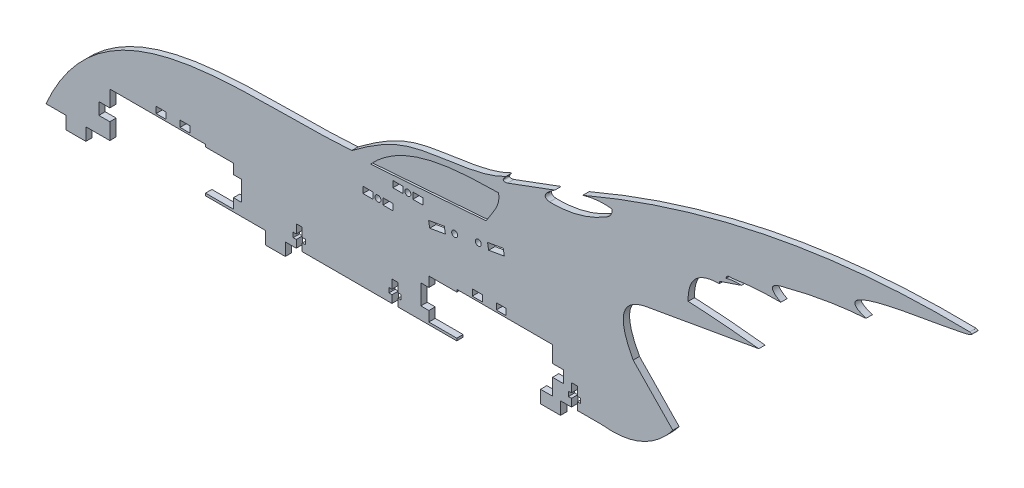
SolidWorks part; units mm, degrees
ref_plane "前视基准面" through (0, 0, 0) normal (0, 0, 1) x (1, 0, 0)
ref_plane "上视基准面" through (0, 0, 0) normal (0, 1, 0) x (1, 0, 0)
ref_plane "右视基准面" through (0, 0, 0) normal (1, 0, 0) x (0, 0, -1)
sketch "Sketch1" plane through (0, 0, 0) normal (0, 0, 1) x (1, 0, 0)
  line L0 (-360, 0) -> (360, 0) construction
  line L1 (-19.5671, 50.1455) -> (753.6757, 55.0373) construction
  line L2 (-32.114, 89.2833) -> (541.2194, 89.2833) construction
sketch "Sketch2" plane through (0, 0, 0) normal (0, 0, 1) x (1, 0, 0)
  line L0 (-171.469, -34.0766) -> (107.0727, -34.0766)
  spline S0 degree 2 poles (291.7809, 98.4714) (190.6089, 100.5394) (97.7379, 60.7759) knots 0 0 0 1 1 1
  spline S1 degree 2 poles (97.7379, 60.7759) (104.9288, 63.0011) (112.3796, 62.1565) knots 0 0 0 1 1 1
  spline S2 degree 2 poles (112.3796, 62.1565) (112.7301, 59.0518) (109.5504, 57.3117) knots 0 0 0 1 1 1
  spline S3 degree 2 poles (109.5504, 57.3117) (96.53, 49.2469) (81.0586, 49.5528) knots 0 0 0 1 1 1
  spline S4 degree 2 poles (81.0586, 49.5528) (75.6423, 50.628) (83.6966, 55.9983) knots 0 0 0 1 1 1
  spline S5 degree 1 poles (83.6966, 55.9983) (60.0234, 47.198) knots 0 0 1 1
  spline S6 degree 2 poles (60.0234, 47.198) (56.1503, 46.2452) (59.1238, 49.6133) knots 0 0 0 1 1 1
  spline S7 degree 3 poles (59.1238, 49.6133) (44.2925, 41.9215) (13.2093, 43.4053) (-7.7072, 29.9938) (-18.1066, 22.3013) knots 0 0 0 0 0.606339 1 1 1 1
  spline S8 degree 3 poles (-18.1066, 22.3013) (-73.3001, 18.1787) (-142.3815, 32.9288) (-171.469, -34.0766) knots 0 0 0 0 1 1 1 1
  spline S9 degree 2 poles (107.0727, -34.0766) (128.9682, -36.583) (142.8921, -18.7155) knots 0 0 0 1 1 1
  spline S10 degree 2 poles (166.2115, 56.6) (150.1116, 56.4482) (150.5886, 41.1327) knots 0 0 0 1 1 1
  spline S11 degree 2 poles (150.5886, 41.1327) (168.3325, 40.2418) (185.983, 38.2447) knots 0 0 0 1 1 1
  spline S12 degree 1 poles (185.983, 38.2447) (129.8121, 28.3469) knots 0 0 1 1
  spline S13 degree 2 poles (129.8121, 28.3469) (110.3675, 24.8357) (122.9996, 1.8225) knots 0 0 0 1 1 1
  spline S14 degree 1 poles (122.9996, 1.8225) (142.8921, -18.7155) knots 0 0 1 1
  spline S25 degree 1 poles (166.2115, 56.6) (166.2327, 57.6697) knots 0 0 1 1
  spline S26 degree 1 poles (166.2327, 57.6697) (177.2433, 61.4033) knots 0 0 1 1
  spline S27 degree 2 poles (177.2433, 61.4033) (173.3395, 61.7966) (169.6271, 60.6108) knots 0 0 0 1 1 1
  spline S28 degree 2 poles (169.6271, 60.6108) (169.7629, 62.5449) (172.4023, 62.1565) knots 0 0 0 1 1 1
  spline S29 degree 2 poles (172.4023, 62.1565) (184.6173, 64.0415) (197.0298, 63.9473) knots 0 0 0 1 1 1
  spline S30 degree 2 poles (197.0298, 63.9473) (187.7347, 69.0696) (198.9644, 71.4021) knots 0 0 0 1 1 1
  spline S31 degree 2 poles (198.9644, 71.4021) (219.0035, 76.7865) (239.7646, 78.3299) knots 0 0 0 1 1 1
  spline S32 degree 3 poles (291.7809, 98.4714) (303.0909, 95.7177) (210.844, 88.0264) (239.7646, 78.3299) knots 0 0 0 0 1 1 1 1
extrude "Boss-Extrude1" add sketch "Sketch2" along normal blind 3.175
sketch "Sketch3" plane through (0, 0, 3.175) normal (0, 0, 1) x (1, 0, 0)
  line L0 (-156.469, -23.0187) -> (-156.469, -49.8356) construction
  line L1 (-161.469, -34.0766) -> (-151.469, -34.0766)
  line L2 (-171.469, -34.0766) -> (107.0727, -34.0766) construction
  line L3 (-161.469, -34.0766) -> (-161.469, -40.4266)
  line L4 (-161.469, -40.4266) -> (-151.469, -40.4266)
  line L5 (-151.469, -40.4266) -> (-151.469, -34.0766)
  line L6 (-106.469, -7.8183) -> (-106.469, -55.0925) construction
  line L7 (-56.469, -23.0187) -> (-56.469, -49.8356) construction
  line L8 (-61.469, -40.4266) -> (-61.469, -34.0766)
  line L9 (-51.469, -40.4266) -> (-61.469, -40.4266)
  line L10 (-51.469, -34.0766) -> (-51.469, -40.4266)
  line L11 (-51.469, -34.0766) -> (-61.469, -34.0766)
  line L12 (-37.469, -5.6354) -> (-37.469, -55.0925) construction
  line L13 (81.531, -23.0187) -> (81.531, -49.8356) construction
  line L14 (76.531, -40.4266) -> (76.531, -34.0766)
  line L15 (86.531, -40.4266) -> (76.531, -40.4266)
  line L16 (86.531, -34.0766) -> (86.531, -40.4266)
  line L17 (86.531, -34.0766) -> (76.531, -34.0766)
  point P6 (-156.469, -34.0766)
  dimension "D1" = 10
  dimension "D2" = 15
  dimension "D3" = 6.35
  dimension "D4" = 100
  dimension "D5" = 238
extrude "Boss-Extrude2" add sketch "Sketch3" against normal blind 3.175
sketch "Sketch4" plane through (0, 0, 3.175) normal (0, 0, 1) x (1, 0, 0)
  line L0 (-8.7353, 21.0767) -> (49.2725, 25.4437)
  spline S0 degree 3 poles (55.4358, 40.7209) (33.0546, 40.3601) (7.8741, 39.273) (-8.7353, 21.0767) knots 0 0 0 0 1 1 1 1
  spline S1 degree 3 poles (55.4358, 40.7209) (56.7107, 34.9555) (51.7522, 29.9519) (49.2725, 25.4437) knots 0 0 0 0 1 1 1 1
extrude "Cut-Extrude1" cut sketch "Sketch4" against normal blind 1
sketch "Sketch5" plane through (0, 0, 3.175) normal (0, 0, 1) x (1, 0, 0)
  line L0 (-44.469, -4.9545) -> (-44.469, -56.9042) construction
  line L1 (-45.969, -34.0766) -> (-42.969, -34.0766)
  line L2 (-151.469, -34.0766) -> (-61.469, -34.0766) construction
  line L3 (-45.969, -34.0766) -> (-45.969, -30.2766)
  line L4 (-45.969, -23.4266) -> (-42.969, -23.4266)
  line L5 (-42.969, -23.4266) -> (-42.969, -27.8766)
  line L6 (-161.469, -40.4266) -> (-151.469, -40.4266) construction
  line L7 (-41.419, -27.8766) -> (-41.419, -30.2766)
  line L8 (-47.519, -27.8766) -> (-47.519, -30.2766)
  line L9 (-47.519, -27.8766) -> (-45.969, -27.8766)
  line L10 (-47.519, -30.2766) -> (-45.969, -30.2766)
  line L11 (-47.519, -29.0766) -> (-93.8427, -29.0766) construction
  line L12 (-161.469, -34.0766) -> (-161.469, -40.4266) construction
  line L13 (-42.969, -27.8766) -> (-41.419, -27.8766)
  line L14 (-42.969, -30.2766) -> (-41.419, -30.2766)
  line L15 (-45.969, -27.8766) -> (-45.969, -23.4266)
  line L16 (-42.969, -30.2766) -> (-42.969, -34.0766)
  line L17 (-20.469, -10.7451) -> (-20.469, -65.5516) construction
  line L18 (3.531, -4.9545) -> (3.531, -56.9042) construction
  line L19 (2.031, -30.2766) -> (2.031, -34.0766)
  line L20 (5.031, -27.8766) -> (5.031, -23.4266)
  line L21 (2.031, -30.2766) -> (0.481, -30.2766)
  line L22 (2.031, -27.8766) -> (0.481, -27.8766)
  line L23 (6.581, -30.2766) -> (5.031, -30.2766)
  line L24 (6.581, -27.8766) -> (5.031, -27.8766)
  line L25 (6.581, -27.8766) -> (6.581, -30.2766)
  line L26 (0.481, -27.8766) -> (0.481, -30.2766)
  line L27 (2.031, -23.4266) -> (2.031, -27.8766)
  line L28 (5.031, -23.4266) -> (2.031, -23.4266)
  line L29 (5.031, -34.0766) -> (5.031, -30.2766)
  line L30 (5.031, -34.0766) -> (2.031, -34.0766)
  line L31 (24.531, -8.6696) -> (24.531, -64.6722) construction
  line L32 (93.531, -4.9545) -> (93.531, -56.9042) construction
  line L33 (92.031, -30.2766) -> (92.031, -34.0766)
  line L34 (95.031, -27.8766) -> (95.031, -23.4266)
  line L35 (92.031, -30.2766) -> (90.481, -30.2766)
  line L36 (92.031, -27.8766) -> (90.481, -27.8766)
  line L37 (96.581, -30.2766) -> (95.031, -30.2766)
  line L38 (96.581, -27.8766) -> (95.031, -27.8766)
  line L39 (96.581, -27.8766) -> (96.581, -30.2766)
  line L40 (90.481, -27.8766) -> (90.481, -30.2766)
  line L41 (92.031, -23.4266) -> (92.031, -27.8766)
  line L42 (95.031, -23.4266) -> (92.031, -23.4266)
  line L43 (95.031, -34.0766) -> (95.031, -30.2766)
  line L44 (95.031, -34.0766) -> (92.031, -34.0766)
  point P6 (-44.469, -34.0766)
  dimension "D1" = 3
  dimension "D2" = 17
  dimension "D3" = 6.1
  dimension "D4" = 5
  dimension "D5" = 117
  dimension "D6" = 2.4
  dimension "D7" = 165
  dimension "D8" = 255
extrude "Cut-Extrude2" cut sketch "Sketch5" against normal through all
sketch "Sketch7" plane through (0, 0, 3.175) normal (0, 0, 1) x (1, 0, 0)
  line L0 (-91.469, -32.8766) -> (-77.469, -32.8766)
  line L1 (-139.469, -34.0766) -> (-139.469, -25.8766)
  line L2 (-151.469, -34.0766) -> (-61.469, -34.0766) construction
  line L3 (-139.469, -11.6766) -> (-91.469, -11.6766)
  line L4 (-91.469, -11.6766) -> (-91.469, -12.8766)
  line L5 (-139.469, -34.0766) -> (-91.469, -34.0766)
  line L6 (-155.6863, -22.8766) -> (-79.2758, -22.8766) construction
  line L7 (-91.469, -12.8766) -> (-77.469, -12.8766)
  line L8 (-77.469, -12.8766) -> (-77.469, -17.8766)
  line L9 (-91.469, -32.8766) -> (-91.469, -34.0766)
  line L10 (-139.469, -19.8766) -> (-144.969, -19.8766)
  line L11 (-139.469, -25.8766) -> (-144.969, -25.8766)
  line L12 (-144.969, -19.8766) -> (-144.969, -25.8766)
  line L13 (-139.469, -19.8766) -> (-139.469, -11.6766)
  line L14 (-77.469, -17.8766) -> (-73.469, -17.8766)
  line L15 (-77.469, -27.8766) -> (-73.469, -27.8766)
  line L16 (-73.469, -17.8766) -> (-73.469, -27.8766)
  line L17 (-77.469, -27.8766) -> (-77.469, -32.8766)
  line L18 (-28.469, 4.1122) -> (-28.469, -62.6854) construction
  line L19 (98.7482, -22.8766) -> (22.3377, -22.8766) construction
  line L20 (20.531, -27.8766) -> (20.531, -32.8766)
  line L21 (16.531, -17.8766) -> (16.531, -27.8766)
  line L22 (20.531, -27.8766) -> (16.531, -27.8766)
  line L23 (20.531, -17.8766) -> (16.531, -17.8766)
  line L24 (82.531, -19.8766) -> (82.531, -11.6766)
  line L25 (88.031, -19.8766) -> (88.031, -25.8766)
  line L26 (82.531, -25.8766) -> (88.031, -25.8766)
  line L27 (82.531, -19.8766) -> (88.031, -19.8766)
  line L28 (34.531, -32.8766) -> (34.531, -34.0766)
  line L29 (20.531, -12.8766) -> (20.531, -17.8766)
  line L30 (34.531, -12.8766) -> (20.531, -12.8766)
  line L31 (82.531, -34.0766) -> (34.531, -34.0766)
  line L32 (34.531, -11.6766) -> (34.531, -12.8766)
  line L33 (82.531, -11.6766) -> (34.531, -11.6766)
  line L34 (82.531, -34.0766) -> (82.531, -25.8766)
  line L35 (34.531, -32.8766) -> (20.531, -32.8766)
  line L36 (-120.2067, -9.1491) -> (-44.1643, -9.1491) construction
  line L37 (-107.769, -0.3828) -> (-107.769, -8.179) construction
  line L38 (-111.269, -10.7366) -> (-116.269, -10.7366)
  line L39 (-111.269, -10.7366) -> (-111.269, -7.5616)
  line L40 (-111.269, -7.5616) -> (-116.269, -7.5616)
  line L41 (-116.269, -10.7366) -> (-116.269, -7.5616)
  line L42 (-111.269, -10.7366) -> (-116.269, -7.5616) construction
  line L43 (-111.269, -7.5616) -> (-116.269, -10.7366) construction
  line L44 (-104.269, -7.5616) -> (-99.269, -10.7366) construction
  line L45 (-104.269, -10.7366) -> (-99.269, -7.5616) construction
  line L46 (-99.269, -10.7366) -> (-99.269, -7.5616)
  line L47 (-104.269, -7.5616) -> (-99.269, -7.5616)
  line L48 (-104.269, -10.7366) -> (-104.269, -7.5616)
  line L49 (-104.269, -10.7366) -> (-99.269, -10.7366)
  line L50 (47.331, -10.7366) -> (42.331, -7.5616) construction
  line L51 (47.331, -7.5616) -> (42.331, -10.7366) construction
  line L52 (54.331, -7.5616) -> (59.331, -10.7366) construction
  line L53 (54.331, -10.7366) -> (59.331, -7.5616) construction
  line L54 (47.331, -10.7366) -> (42.331, -10.7366)
  line L55 (47.331, -10.7366) -> (47.331, -7.5616)
  line L56 (47.331, -7.5616) -> (42.331, -7.5616)
  line L57 (42.331, -10.7366) -> (42.331, -7.5616)
  line L58 (59.331, -10.7366) -> (59.331, -7.5616)
  line L59 (54.331, -7.5616) -> (59.331, -7.5616)
  line L60 (54.331, -10.7366) -> (54.331, -7.5616)
  line L61 (54.331, -10.7366) -> (59.331, -10.7366)
  point P43 (-113.769, -9.1491)
  point P54 (-101.769, -9.1491)
  point P63 (44.831, -9.1491)
  point P64 (56.831, -9.1491)
  dimension "D3" = 48
  dimension "D1" = 32
  dimension "D2" = 22.4
  dimension "D4" = 20
  dimension "D5" = 14
  dimension "D6" = 6
  dimension "D7" = 5.5
  dimension "D8" = 4
  dimension "D9" = 10
  dimension "D10" = 90
  dimension "D11" = 12
  dimension "D12" = 23.2
  dimension "D13" = 0.94
  dimension "D14" = 3.175
  dimension "D15" = 5
extrude "Cut-Extrude3" cut sketch "Sketch7" against normal through all
sketch "Sketch8" plane through (0, 0, 3.175) normal (0, 0, 1) x (1, 0, 0)
  line L0 (0, 0) -> (0, 6) construction
  line L1 (0, 6) -> (50.4572, 14.897) construction
  line L2 (32.7597, 50.5612) -> (39.3923, 12.9459) construction
  line L3 (20.9566, 8.0832) -> (28.8351, 9.4724)
  line L4 (28.8351, 9.4724) -> (28.2838, 12.5992)
  line L5 (20.9566, 8.0832) -> (20.4053, 11.21)
  line L6 (20.4053, 11.21) -> (28.2838, 12.5992)
  line L7 (24.8959, 8.7778) -> (23.4697, 16.8657) construction
  line L8 (54.4401, 13.9873) -> (53.014, 22.0752) construction
  line L9 (57.828, 17.8086) -> (49.9495, 16.4194)
  line L10 (58.3793, 14.6819) -> (57.828, 17.8086)
  line L11 (50.5009, 13.2927) -> (49.9495, 16.4194)
  line L12 (58.3793, 14.6819) -> (50.5009, 13.2927)
  circle A0 centre (33.4835, 11.904) radius 1.5
  circle A1 centre (45.3012, 13.9878) radius 1.5
  point P8 (28.5594, 11.0358)
  dimension "D7" = 3
  dimension "D1" = 6
  dimension "D2" = 100
  dimension "D3" = 40
  dimension "D4" = 3.175
  dimension "D5" = 8
  dimension "D6" = 30
  dimension "D8" = 12
extrude "Cut-Extrude4" cut sketch "Sketch8" against normal through all
sketch "Sketch9" plane through (0, 0, 3.175) normal (0, 0, 1) x (1, 0, 0)
  line L0 (10, 32.0127) -> (10, 0) construction
  line L1 (-14.9157, 18) -> (23.6696, 18) construction
  line L2 (2.5, 19.5875) -> (7.5, 16.4125) construction
  line L3 (17.5, 16.4125) -> (12.5, 16.4125)
  line L4 (17.5, 16.4125) -> (17.5, 19.5875)
  line L5 (17.5, 19.5875) -> (12.5, 19.5875)
  line L6 (12.5, 16.4125) -> (12.5, 19.5875)
  line L7 (17.5, 16.4125) -> (12.5, 19.5875) construction
  line L8 (17.5, 19.5875) -> (12.5, 16.4125) construction
  line L9 (2.5, 16.4125) -> (7.5, 19.5875) construction
  line L10 (7.5, 16.4125) -> (7.5, 19.5875)
  line L11 (2.5, 19.5875) -> (7.5, 19.5875)
  line L12 (2.5, 16.4125) -> (2.5, 19.5875)
  line L13 (2.5, 16.4125) -> (7.5, 16.4125)
  line L14 (-5, 12.4125) -> (-5, -3.1137) construction
  line L15 (-20.9752, 8) -> (1.55, 8) construction
  line L17 (-12.5, 6.4125) -> (-7.5, 6.4125)
  line L18 (-12.5, 6.4125) -> (-12.5, 9.5875)
  line L19 (2.5, 6.4125) -> (-2.5, 9.5875) construction
  line L20 (-7.5, 6.4125) -> (-7.5, 9.5875)
  line L21 (-12.5, 9.5875) -> (-7.5, 6.4125) construction
  line L23 (-12.5, 9.5875) -> (-7.5, 9.5875)
  line L25 (2.5, 9.5875) -> (-2.5, 6.4125) construction
  line L26 (-12.5, 6.4125) -> (-7.5, 9.5875) construction
  line L28 (2.5, 9.5875) -> (-2.5, 9.5875)
  line L29 (-2.5, 6.4125) -> (-2.5, 9.5875)
  line L30 (2.5, 6.4125) -> (2.5, 9.5875)
  line L31 (2.5, 6.4125) -> (-2.5, 6.4125)
  circle A0 centre (10, 18) radius 1.5
  circle A1 centre (-5, 8) radius 1.5
  point P4 (15, 18)
  point P14 (5, 18)
  point P25 (0, 8)
  point P30 (-10, 8)
  point P33 (0, 0)
  point P34 (-12.5, 8)
  dimension "D6" = 3
  dimension "D7" = 8
  dimension "D12" = 3
  dimension "D1" = 10
  dimension "D2" = 18
  dimension "D3" = 3.175
  dimension "D4" = 5
  dimension "D5" = 5
  dimension "D8" = 5
  dimension "D9" = 5
  dimension "D10" = 3.175
  dimension "D11" = 10
extrude "Cut-Extrude5" cut sketch "Sketch9" against normal through all
